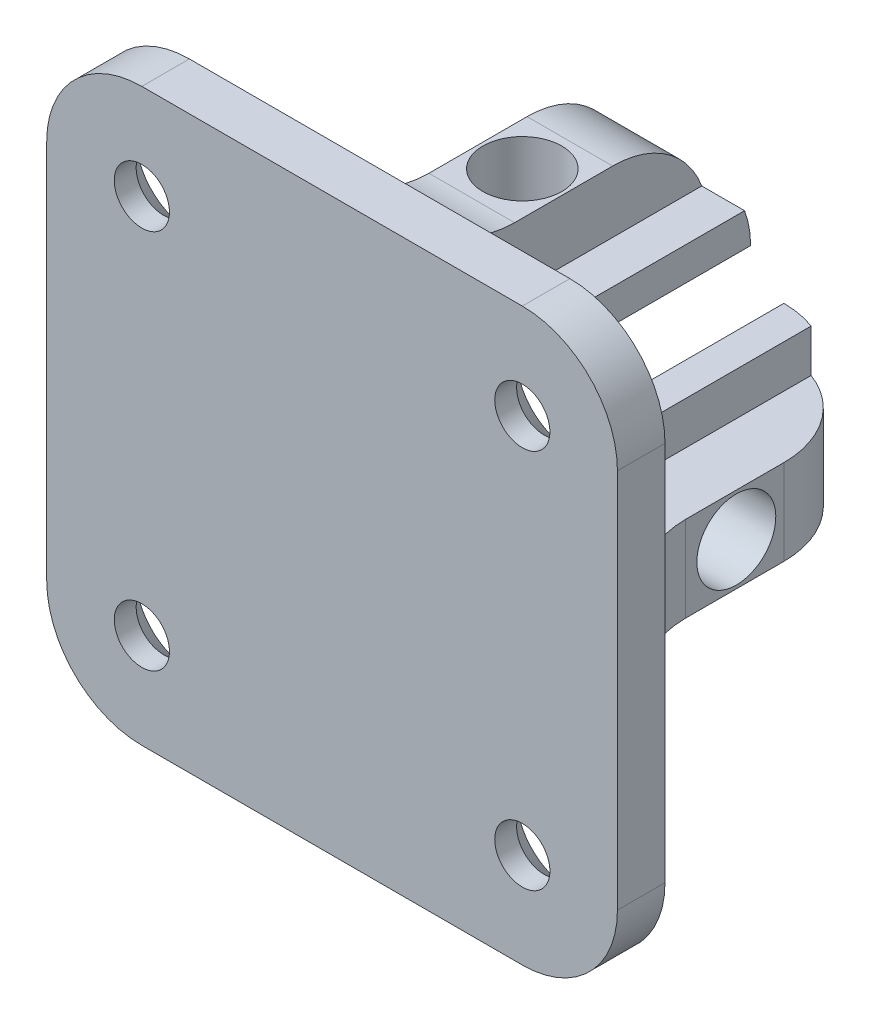
SolidWorks part; units mm, degrees
ref_plane "Front Plane" through (0, 0, 0) normal (0, 0, 1) x (1, 0, 0)
ref_plane "Top Plane" through (0, 0, 0) normal (0, 1, 0) x (1, 0, 0)
ref_plane "Right Plane" through (0, 0, 0) normal (1, 0, 0) x (0, 0, -1)
sketch "Sketch1" plane through (0, 0, 0) normal (0, 0, 1) x (1, 0, 0)
  line L0 (-45, 45) -> (0, 0) construction
  line L1 (-52.5, -7.5) -> (7.5, -7.5)
  line L2 (-52.5, -7.5) -> (-52.5, 52.5)
  line L3 (-52.5, 52.5) -> (7.5, 52.5)
  line L4 (7.5, -7.5) -> (7.5, 52.5)
  line L5 (-52.5, -7.5) -> (7.5, 52.5) construction
  line L6 (-52.5, 52.5) -> (7.5, -7.5) construction
  line L7 (0, 0) -> (-45, 0) construction
  line L8 (0, 0) -> (0, 45) construction
  line L9 (0, 45) -> (-45, 45) construction
  line L10 (-45, 0) -> (-45, 45) construction
  line L11 (0, 45) -> (-45, 0) construction
  line L13 (-52.5, 12.5) -> (-45.5, 12.5)
  line L14 (-52.5, 12.5) -> (-52.5, 32.5)
  line L15 (-52.5, 32.5) -> (-45.5, 32.5)
  line L16 (-45.5, 12.5) -> (-45.5, 32.5)
  line L17 (-45.5, 26.75) -> (-42.5, 26.75)
  line L18 (-45.5, 26.75) -> (-45.5, 18.25)
  line L19 (-45.5, 18.25) -> (-42.5, 18.25)
  line L20 (-42.5, 26.75) -> (-42.5, 18.25)
  point P0 (-22.5, 22.5)
  point P10 (-22.5, 22.5)
  point P19 (-52.5, 22.5)
  point P20 (-45.5, 22.5)
  point P22 (-2.5, 42.5)
  point P49 (-2.5, 2.5)
  point P50 (-42.5, 2.5)
  point P51 (-42.5, 42.5)
  dimension "D1" = 60
  dimension "D2" = 60
  dimension "D3" = 45
  dimension "D4" = 45
  dimension "D5" = 20
  dimension "D6" = 7
  dimension "D7" = 8.5
  dimension "D8" = 3
  dimension "D10" = 10
  dimension "D11" = 4
extrude "Boss-Extrude1" add sketch "Sketch1" along normal blind 5 contours L1 L4 L3 L2 L15 L16 L17 L20 L19 L13 | L13 L16 L15 L2 | L20 L17 L16 L19 | L3 | L4 | L1 region at (-21.2602, 22.5, 0) region at (-49, 22.5, 0) region at (-44, 22.5, 0)
hole_wizard "CSK for M5 Hex Socket Countersunk Cap Screw1" positions "Sketch6" profile "Sketch7" countersink size "M5" standard "ISO"
sketch "Sketch6" plane through (0, 0, 0) normal (0, 0, -1) x (-1, 0, 0)
  point P0 (2.5, 42.5)
  point P3 (42.5, 42.5)
  point P6 (42.5, 2.5)
  point P9 (2.5, 2.5)
sketch "Sketch7" plane through (-2.5, 42.5, 0) normal (1, 0, 0) x (0, 1, 0)
  line L0 (0, 0) -> (0, 6.7425)
  line L1 (0, 6.7425) -> (2.9, 5)
  line L2 (2.9, 5) -> (2.9, 2.7)
  line L3 (2.9, 2.7) -> (5.6, 0)
  line L5 (5.6, 0) -> (0, 0)
  line L6 (-2.9, 2.7) -> (-5.6, 0) construction
  line L10 (0, 6.7425) -> (-2.9, 5) construction
  line L11 (0, -6.35) -> (0, 107.95) construction
  dimension "Hole Dia." = 5.8
  dimension "Hole Depth" = 5
  dimension "Near C'Sink Dia." = 11.2
  dimension "Near C'Sink Angle" = 90
  dimension "Drill Angle" = 118
ref_axis "Axis1" through (-22.5, 22.5, 0) along (0, 0, -1)
sketch "Sketch8" plane through (0, 0, 0) normal (0, 0, -1) x (-1, 0, 0)
  line L0 (27, 0) -> (27, 6.5)
  line L1 (27, 6.5) -> (31.5, 6.5)
  line L2 (31.5, 6.5) -> (31.5, 10)
  line L3 (31.5, 10) -> (27.2574, 14.2426)
  line L4 (27.2574, 14.2426) -> (17.7426, 14.2426)
  line L5 (22.5, -7.5) -> (22.5, 14.2426) construction
  line L6 (52.5, -7.5) -> (-7.5, -7.5) construction
  line L7 (27, 0) -> (18, 0)
  line L8 (13.5, 10) -> (17.7426, 14.2426)
  line L9 (13.5, 6.5) -> (13.5, 10)
  line L10 (18, 6.5) -> (13.5, 6.5)
  line L11 (18, 0) -> (18, 6.5)
  line L12 (-7.5, 22.5) -> (52.5, 22.5) construction
  line L13 (-7.5, -7.5) -> (-7.5, 52.5) construction
  line L14 (52.5, -7.5) -> (52.5, 52.5) construction
  line L15 (22.5, 52.5) -> (22.5, -7.5) construction
  line L16 (52.5, 52.5) -> (-7.5, 52.5) construction
  line L17 (0, 18) -> (6.5, 18)
  line L18 (6.5, 18) -> (6.5, 13.5)
  line L19 (6.5, 13.5) -> (10, 13.5)
  line L20 (10, 13.5) -> (14.2426, 17.7426)
  line L21 (14.2426, 17.7426) -> (14.2426, 27.2574)
  line L22 (0, 18) -> (0, 27)
  line L23 (10, 31.5) -> (14.2426, 27.2574)
  line L24 (6.5, 31.5) -> (10, 31.5)
  line L25 (6.5, 27) -> (6.5, 31.5)
  line L26 (0, 27) -> (6.5, 27)
  line L27 (18, 45) -> (18, 38.5)
  line L28 (18, 38.5) -> (13.5, 38.5)
  line L29 (13.5, 38.5) -> (13.5, 35)
  line L30 (13.5, 35) -> (17.7426, 30.7574)
  line L31 (17.7426, 30.7574) -> (27.2574, 30.7574)
  line L32 (18, 45) -> (27, 45)
  line L33 (31.5, 35) -> (27.2574, 30.7574)
  line L34 (31.5, 38.5) -> (31.5, 35)
  line L35 (27, 38.5) -> (31.5, 38.5)
  line L36 (27, 45) -> (27, 38.5)
  line L37 (45, 27) -> (38.5, 27)
  line L38 (38.5, 27) -> (38.5, 31.5)
  line L39 (38.5, 31.5) -> (35, 31.5)
  line L40 (35, 31.5) -> (30.7574, 27.2574)
  line L41 (30.7574, 27.2574) -> (30.7574, 17.7426)
  line L42 (45, 27) -> (45, 18)
  line L43 (35, 13.5) -> (30.7574, 17.7426)
  line L44 (38.5, 13.5) -> (35, 13.5)
  line L45 (38.5, 18) -> (38.5, 13.5)
  line L46 (45, 18) -> (38.5, 18)
  line L48 (0, 45) -> (45, 45) construction
  line L49 (0, 45) -> (0, 0) construction
  line L50 (0, 0) -> (45, 0) construction
  line L51 (45, 45) -> (45, 0) construction
  line L52 (0, 45) -> (45, 0) construction
  line L53 (0, 0) -> (45, 45) construction
  point P10 (22.5, 0)
  point P22 (22.5, 22.5)
  point P34 (0, 22.5)
  point P45 (22.5, 45)
  point P56 (45, 22.5)
  point P62 (22.5, 22.5)
  point P63 (22.5, 45)
  dimension "D1" = 4.5
  dimension "D2" = 6.5
  dimension "D3" = 45
  dimension "D4" = 4.5
  dimension "D5" = 3.5
  dimension "D6" = 6
  dimension "D7" = 135
  dimension "D9" = 45
  dimension "D8" = 4
extrude "Boss-Extrude2" add sketch "Sketch8" along normal blind 30
fillet "Fillet1" radius 10 8 edges at (-22.5, 45, 0) (-45, 22.5, 0) (-45, 22.5, -30) (-22.5, 45, -30) (0, 22.5, -30) (0, 22.5, 0) (-22.5, 0, 0) (-22.5, 0, -30)
sketch "Sketch11" plane through (0, 14.2426, 0) normal (0, 1, 0) x (1, 0, 0)
  line L0 (-22.5, 30) -> (-22.5, 15) construction
  line L1 (-27.2574, 30) -> (-17.7426, 30) construction
  circle A0 centre (-22.5, 15) radius 4.15
  dimension "D1" = 8.3
  dimension "D2" = 15
extrude "Cut-Extrude1" cut sketch "Sketch11" against normal up to next
pattern_circular "CirPattern1" count 4 over 360 about axis through (-22.5, 22.5, 0) along (0, 0, -1) of "Cut-Extrude1"
fillet "Fillet2" radius 10 4 edges at (-52.5, -7.5, 2.5) (7.5, -7.5, 2.5) (7.5, 52.5, 2.5) (-52.5, 52.5, 2.5)
sketch "Sketch12" plane through (-30.7574, 0, 0) normal (1, 0, 0) x (0, 0, -1)
  line L1 (11.1029, 15.75) -> (18.8971, 15.75)
  line L2 (18.8971, 15.75) -> (22.7942, 22.5)
  line L3 (22.7942, 22.5) -> (18.8971, 29.25)
  line L4 (18.8971, 29.25) -> (11.1029, 29.25)
  line L5 (11.1029, 29.25) -> (7.2058, 22.5)
  line L6 (7.2058, 22.5) -> (11.1029, 15.75)
  circle A0 centre (15, 22.5) radius 6.75 construction
  dimension "D1" = 13.5
extrude "Cut-Extrude2" cut sketch "Sketch12" against normal blind 6.5
pattern_circular "CirPattern2" count 4 over 360 about axis through (-22.5, 22.5, 0) along (0, 0, -1) of "Cut-Extrude2"
